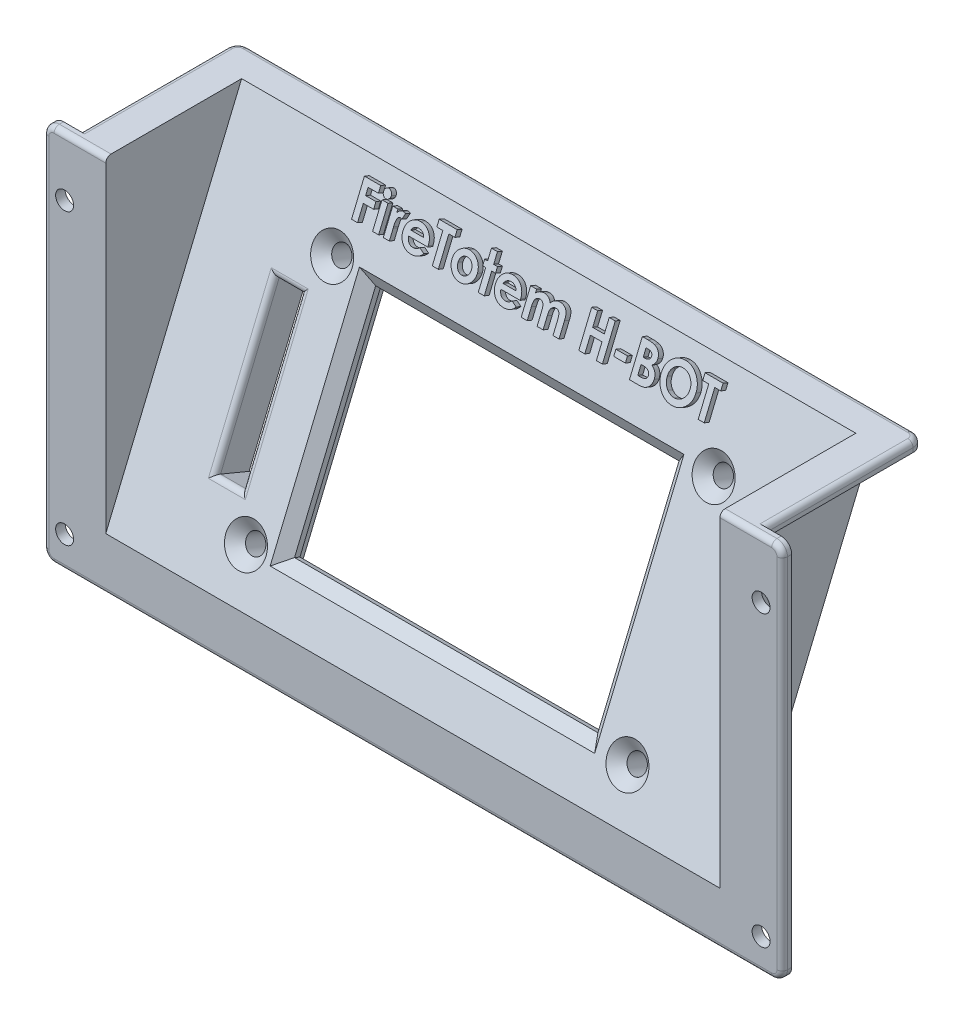
SolidWorks part; units mm, degrees
material "Настроенная пользователем пластмасса"
ref_plane "Front" through (0, 0, 0) normal (0, 0, 1) x (1, 0, 0)
ref_plane "Top" through (0, 0, 0) normal (0, 1, 0) x (1, 0, 0)
ref_plane "Right" through (0, 0, 0) normal (1, 0, 0) x (0, 0, -1)
sketch "Эскиз1" plane through (0, 0, 0) normal (0, 0, 1) x (1, 0, 0)
  line L0 (-58.2, 35.9) -> (-58.2, -25.9)
  line L1 (-68, 35.9) -> (-58.2, 35.9)
  line L2 (-70, 33.9) -> (-70, -33.9)
  line L3 (-68, -35.9) -> (68, -35.9)
  line L4 (70, 33.9) -> (70, -33.9)
  line L5 (-70, 35.9) -> (70, -35.9) construction
  line L6 (-70, -35.9) -> (70, 35.9) construction
  line L7 (-58.2, -25.9) -> (58.2, -25.9)
  line L8 (58.2, -25.9) -> (58.2, 35.9)
  line L9 (58.2, 35.9) -> (68, 35.9)
  circle A0 centre (-66, -29.9) radius 1.7
  circle A1 centre (66, -29.9) radius 1.7
  circle A2 centre (-66, 24.9) radius 1.7
  circle A3 centre (66, 24.9) radius 1.7
  arc A4 (-70, -33.9) -> (-68, -35.9) centre (-68, -33.9) ccw
  arc A5 (68, -35.9) -> (70, -33.9) centre (68, -33.9) ccw
  arc A6 (68, 35.9) -> (70, 33.9) centre (68, 33.9) cw
  arc A7 (-68, 35.9) -> (-70, 33.9) centre (-68, 33.9) ccw
  point P0 (0, 0)
  dimension "D5" = 3.4
  dimension "D7" = 6
  dimension "D8" = 3.4
  dimension "D9" = 4
  dimension "D10" = 6
  dimension "D11" = 3.4
  dimension "D14" = 3.4
  dimension "D16" = 2
  dimension "D1" = 140
  dimension "D2" = 71.8
  dimension "D3" = 11.8
  dimension "D4" = 11.8
  dimension "D6" = 4
  dimension "D12" = 11
  dimension "D13" = 4
  dimension "D15" = 10
extrude "Бобышка-Вытянуть1" add sketch "Эскиз1" along normal blind 1.8
sketch "Эскиз2" plane through (0, 35.9, 0) normal (0, 1, 0) x (1, 0, 0)
  line L0 (-58.2, 0) -> (-58.2, 24)
  line L1 (-58.2, 24) -> (58.2, 24)
  line L2 (58.2, 24) -> (58.2, 0)
  line L3 (58.2, 0) -> (65, 0)
  line L4 (68, 0) -> (58.2, 0) construction
  line L5 (65, 0) -> (65, 28)
  line L6 (63, 30) -> (-63, 30)
  line L7 (-65, 28) -> (-65, 0)
  line L8 (-58.2, 0) -> (-68, 0) construction
  line L9 (-65, 0) -> (-58.2, 0)
  arc A0 (65, 28) -> (63, 30) centre (63, 28) ccw
  arc A1 (-63, 30) -> (-65, 28) centre (-63, 28) ccw
  dimension "D5" = 2
  dimension "D1" = 6.8
  dimension "D2" = 24
  dimension "D3" = 6
  dimension "D4" = 6.8
extrude "Бобышка-Вытянуть2" add sketch "Эскиз2" against normal blind 1.8
sketch "Эскиз3" plane through (58.2, 0, 0) normal (-1, 0, 0) x (0, 0, 1)
  line L2 (-25, 34.1) -> (0, -25.9)
  line L4 (1.8, 33.9) -> (1.8, -33.9) construction
  line L5 (1.8, -25.9) -> (-23.95, 35.9)
  line L6 (-28, 35.9) -> (0, 35.9) construction
  line L8 (0, -25.9) -> (1.8, -25.9)
  line L9 (-25, 34.1) -> (-25, 35.9)
  line L11 (-23.95, 35.9) -> (-25, 35.9)
extrude "Бобышка-Вытянуть3" add sketch "Эскиз3" along normal up to surface (116.4 mm away) up to face at (-58.2, 14.7, -7.4)
sketch "Эскиз4" plane through (-58.2, 0, 0) normal (-1, 0, 0) x (0, 0, 1)
  line L0 (-25, 34.1) -> (0, -25.9)
  line L1 (0, -25.9) -> (0, 34.1)
  line L2 (0, 34.1) -> (-25, 34.1)
extrude "Бобышка-Вытянуть4" add sketch "Эскиз4" along normal blind 1.8
sketch "Эскиз5" plane through (58.2, 0, 0) normal (1, 0, 0) x (0, 0, -1)
  line L0 (25, 34.1) -> (0, 34.1)
  line L1 (0, 34.1) -> (0, -25.9)
  line L2 (0, -25.9) -> (25, 34.1)
extrude "Бобышка-Вытянуть5" add sketch "Эскиз5" along normal blind 1.8
sketch "Эскиз6" plane through (0, -3.8314, -9.1953) normal (0, -0.3846, -0.9231) x (-1, 0, 0)
  line L0 (60, 41.0923) -> (-60, 41.0923) construction
  line L1 (-43.3, 31.6223) -> (48, 31.6223)
  line L2 (-43.3, 31.6223) -> (-43.3, -20.1277)
  line L3 (-43.3, -20.1277) -> (48, -20.1277)
  line L4 (48, 31.6223) -> (48, -20.1277)
  line L5 (-60, -23.9077) -> (-60, 41.0923) construction
  line L6 (60, 41.0923) -> (60, -23.9077) construction
  line L8 (-60, -23.9077) -> (60, -23.9077) construction
  dimension "D1" = 9.47
  dimension "D2" = 16.7
  dimension "D3" = 12
  dimension "D4" = 51.75
  dimension "D5" = 3.78
extrude "Бобышка-Вытянуть6" add sketch "Эскиз6" along normal blind 5.2
sketch "Эскиз7" plane through (0, -5.8314, -13.9953) normal (0, -0.3846, -0.9231) x (-1, 0, 0)
  line L0 (48, 31.6223) -> (-43.3, 31.6223) construction
  line L1 (43.28, 19.7723) -> (38.28, 19.7723)
  line L2 (43.28, 19.7723) -> (43.28, -9.2277)
  line L3 (43.28, -9.2277) -> (38.28, -9.2277)
  line L4 (38.28, 19.7723) -> (38.28, -9.2277)
  line L5 (48, -20.1277) -> (48, 31.6223) construction
  dimension "D1" = 11.85
  dimension "D2" = 5
  dimension "D3" = 4.72
  dimension "D4" = 29
extrude "Вырез-Вытянуть1" cut sketch "Эскиз7" against normal up to surface (6.8615 mm away) up to face at (0, 5, -11.075)
sketch "Эскиз8" plane through (0, -5.8314, -13.9953) normal (0, -0.3846, -0.9231) x (-1, 0, 0)
  line L0 (48, 31.6223) -> (-43.3, 31.6223) construction
  line L1 (-32.69, 27.9223) -> (30.31, 27.9223)
  line L2 (-32.69, 27.9223) -> (-32.69, -17.0777)
  line L3 (-32.69, -17.0777) -> (30.31, -17.0777)
  line L4 (30.31, 27.9223) -> (30.31, -17.0777)
  line L5 (-43.3, 31.6223) -> (-43.3, -20.1277) construction
  dimension "D1" = 63
  dimension "D2" = 45
  dimension "D3" = 3.7
  dimension "D4" = 10.61
extrude "Вырез-Вытянуть2" cut sketch "Эскиз8" against normal blind 3.75
sketch "Эскиз9" plane through (0, -4.3891, -10.5337) normal (0, -0.3846, -0.9231) x (-1, 0, 0)
  line L0 (30.31, -17.0777) -> (30.31, 27.9223) construction
  line L1 (-29.44, 25.2423) -> (28.06, 25.2423)
  line L2 (-29.44, 25.2423) -> (-29.44, -14.7577)
  line L3 (-29.44, -14.7577) -> (28.06, -14.7577)
  line L4 (28.06, 25.2423) -> (28.06, -14.7577)
  line L5 (-32.69, 27.9223) -> (-32.69, -17.0777) construction
  line L6 (30.31, 27.9223) -> (-32.69, 27.9223) construction
  line L7 (-32.69, -17.0777) -> (30.31, -17.0777) construction
  dimension "D1" = 2.25
  dimension "D2" = 3.25
  dimension "D3" = 2.68
  dimension "D4" = 2.32
extrude "Вырез-Вытянуть3" cut sketch "Эскиз9" against normal up to surface (3.1115 mm away) up to face at (-40.78, 1.6744, -9.6893)
sketch "Эскиз10" plane through (0, -5.8314, -13.9953) normal (0, -0.3846, -0.9231) x (-1, 0, 0)
  line L0 (48, 31.6223) -> (-43.3, 31.6223) construction
  line L1 (-43.3, 31.6223) -> (-43.3, -20.1277) construction
  line L2 (-43.3, -20.1277) -> (48, -20.1277) construction
  line L3 (48, -20.1277) -> (48, 31.6223) construction
  line L4 (48, 31.6223) -> (-43.3, 31.6223) construction
  circle A0 centre (-37.3, 26.6223) radius 1.8
  circle A1 centre (-37.3, -15.8277) radius 1.8
  circle A2 centre (35, 26.6223) radius 1.8
  circle A3 centre (35, -15.8277) radius 1.8
  dimension "D1" = 3.6
  dimension "D4" = 3.6
  dimension "D7" = 3.6
  dimension "D9" = 3.6
  dimension "D11" = 4.3
  dimension "D12" = 5
  dimension "D2" = 5
  dimension "D3" = 6
  dimension "D5" = 4.3
  dimension "D6" = 6
  dimension "D8" = 13
  dimension "D10" = 13
extrude "Вырез-Вытянуть4" cut sketch "Эскиз10" against normal up to surface (6.8615 mm away) up to face at (0.69, 1.6467, -9.6778)
fillet "Скругление1" radius 1 14 edges at (70, 0, 1.8) (0, -35.9, 1.8) (-70, 0, 1.8) (-65, 35.9, -14) (0, 35.9, -30) (65, 35.9, -14) (63.1, 35.9, 1.8) (-63.1, 35.9, 1.8) (69.4142, 35.3142, 1.8) (69.4142, -35.3142, 1.8) (-69.4142, -35.3142, 1.8) (-69.4142, 35.3142, 1.8) (-64.4142, 35.9, -29.4142) (64.4142, 35.9, -29.4142)
chamfer "Фаска1" distance 2 angle 45 8 edges at (37.3, 23.0437, -18.5932) (37.3, -16.1409, -2.2663) (-35, -16.1409, -2.2663) (-35, 23.0437, -18.5932) (0.69, -16.8148, -1.9855) (-28.06, 1.6467, -9.6778) (0.69, 20.1083, -17.3701) (29.44, 1.6467, -9.6778)
fillet "Скругление2" radius 1 4 edges at (-40.78, -11.7102, -4.1124) (-38.28, 1.6744, -9.6893) (-40.78, 15.0591, -15.2663) (-43.28, 1.6744, -9.6893)
sketch "Эскиз12" plane through (0, -3.1923, -7.6615) normal (0, 0.3846, 0.9231) x (1, 0, 0)
  line L0 (-51.6305, 33.0753) -> (52.7064, 33.0753) construction
  text T0 "<b>FireTotem H-BOT</b>"
extrude "Бобышка-Вытянуть7" add sketch "Эскиз12" along normal blind 1
